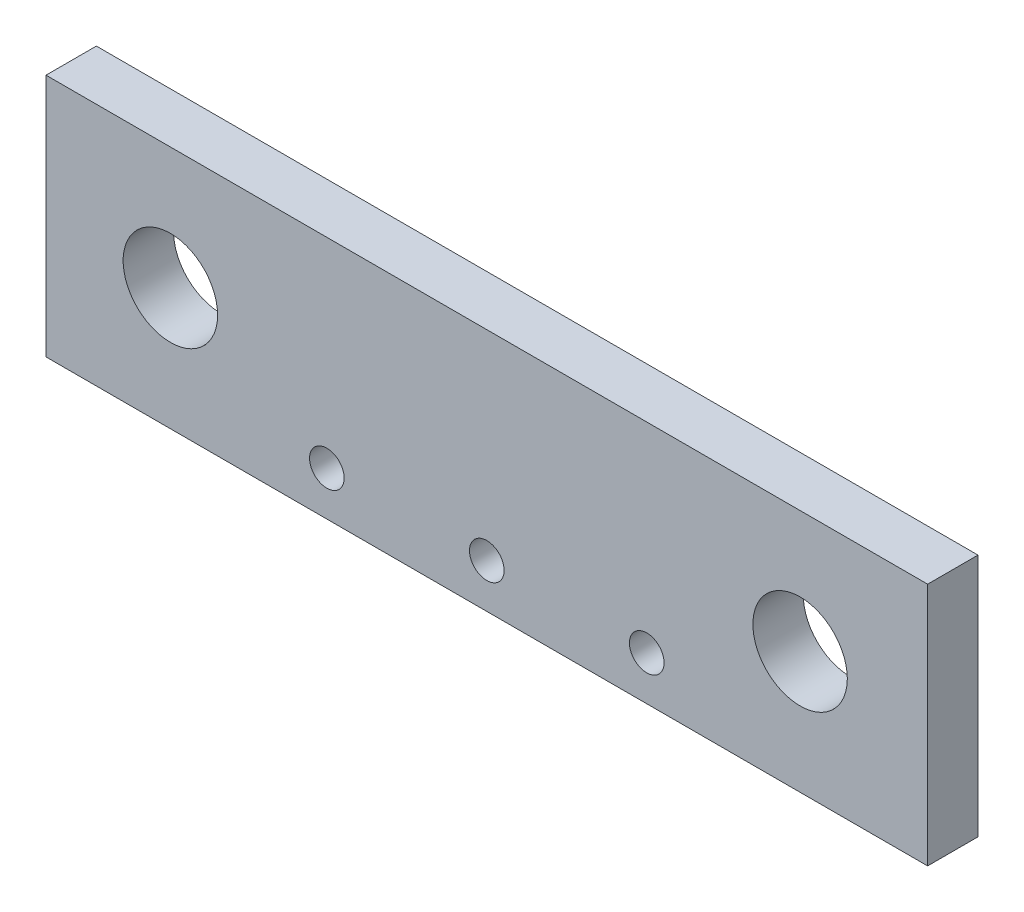
SolidWorks part; units mm, degrees
ref_plane "Front Plane" through (0, 0, 0) normal (0, 0, 1) x (1, 0, 0)
ref_plane "Top Plane" through (0, 0, 0) normal (0, 1, 0) x (1, 0, 0)
ref_plane "Right Plane" through (0, 0, 0) normal (1, 0, 0) x (0, 0, -1)
sketch "Sketch1" plane through (0, 0, 0) normal (0, 0, 1) x (1, 0, 0)
  line L1 (-14, -3.875) -> (14, -3.875)
  line L2 (-14, -3.875) -> (-14, 3.875)
  line L3 (-14, 3.875) -> (14, 3.875)
  line L4 (14, -3.875) -> (14, 3.875)
  line L5 (-14, -3.875) -> (14, 3.875) construction
  line L6 (-14, 3.875) -> (14, -3.875) construction
  point P0 (0, 0)
  dimension "D1" = 28
  dimension "D2" = 7.75
extrude "Boss-Extrude1" add sketch "Sketch1" along normal blind 1.6
sketch "Sketch2" plane through (0, 0, 1.6) normal (0, 0, 1) x (1, 0, 0)
  line L0 (-1000, 0) -> (49000, 0) construction
  line L1 (-14, 3.875) -> (-14, -3.875) construction
  circle A0 centre (-10.05, 0) radius 1.5
  circle A1 centre (9.95, 0) radius 1.5
  dimension "D3" = 3
  dimension "D4" = 3
  dimension "D1" = 3.95
  dimension "D2" = 23.95
extrude "Cut-Extrude1" cut sketch "Sketch2" against normal through all
sketch "Sketch3" plane through (0, 0, 1.6) normal (0, 0, 1) x (1, 0, 0)
  line L0 (0, -1000) -> (0, 49000) construction
  line L1 (-1000, -2.475) -> (49000, -2.475) construction
  line L2 (-14, -3.875) -> (14, -3.875) construction
  circle A0 centre (0, -2.475) radius 0.55
  circle A1 centre (-5.08, -2.475) radius 0.55
  circle A2 centre (5.08, -2.475) radius 0.55
  dimension "D2" = 1.1
  dimension "D3" = 1.1
  dimension "D4" = 1.1
  dimension "D1" = 1.4
  dimension "D5" = 5.08
  dimension "D6" = 5.08
extrude "Cut-Extrude2" cut sketch "Sketch3" against normal through all
